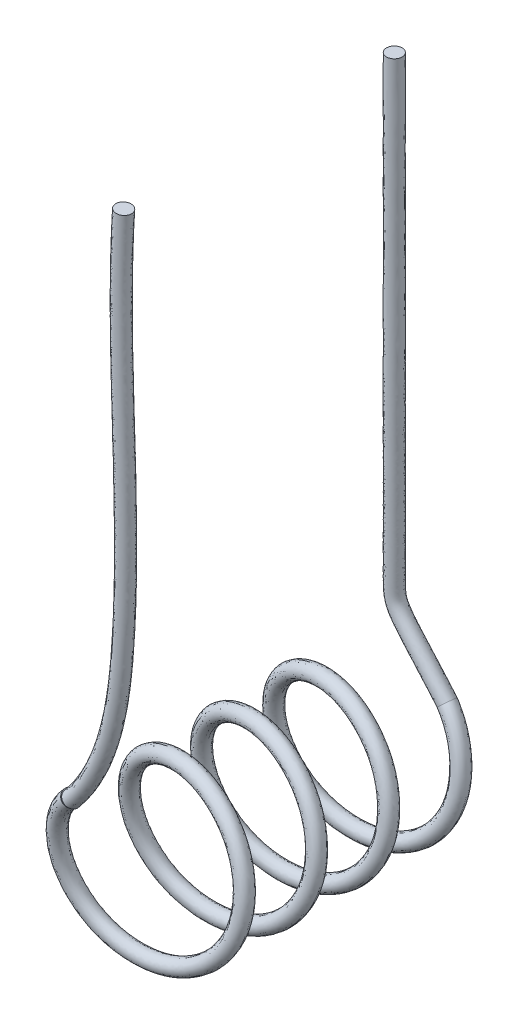
SolidWorks part; units mm, degrees
ref_plane "Front Plane" through (0, 0, 0) normal (0, 0, 1) x (1, 0, 0)
ref_plane "Top Plane" through (0, 0, 0) normal (0, 1, 0) x (1, 0, 0)
ref_plane "Right Plane" through (0, 0, 0) normal (1, 0, 0) x (0, 0, -1)
sketch "Sketch1" plane through (0, 0, 0) normal (0, 0, 1) x (1, 0, 0)
  circle A0 centre (0, 0) radius 0.9652
  dimension "D1" = 1.9304
curve "Helix/Spiral1" pitch 0.9333 height 3.4999 radius 0.9652 left hand yes centre (0, 0, 0) axis (0, 0, 1) start towards (0.7071, 0.7071, 0)
ref_plane "Plane4" through (0, 0, 3.5) normal (0, 0, 1) x (1, 0, 0)
sketch "Sketch16" plane through (0, 0, 3.5) normal (0, 0, 1) x (1, 0, 0)
  line L0 (0, 0) -> (0, 4.011) construction
  spline S0 degree 3 poles (-0.6742, 0.6744) (-0.1572, 1.2904) (0.1834, 3.7284) (-0.1015, 6.0207) (0, 7.62) knots 0 0 0 0 0.331967 1 1 1 1
  dimension "D1" = 7.62
sketch "Sketch17" plane through (0, 0, 0) normal (0, 0, 1) x (1, 0, 0)
  line L0 (0, 0) -> (0, 4.3257) construction
  spline S0 degree 3 poles (0.6825, 0.6825) (0.008, 1.4664) (-0.0017, 1.3595) (0.0011, 2.8955) (-0.0007, 2.9904) (0, 7.62) knots 0 0 0 0 0.357027 0.532141 1 1 1 1
  dimension "D1" = 7.62
sweep "Sweep1" add path "Sketch17" circular profile diameter 0.2032 parameters "D3"=0.2032
sweep "Sweep2" add path "Helix/Spiral1" circular profile diameter 0.2032 parameters "D3"=0.2032
sweep "Sweep3" add path "Sketch16" circular profile diameter 0.2032 parameters "D3"=0.2032
